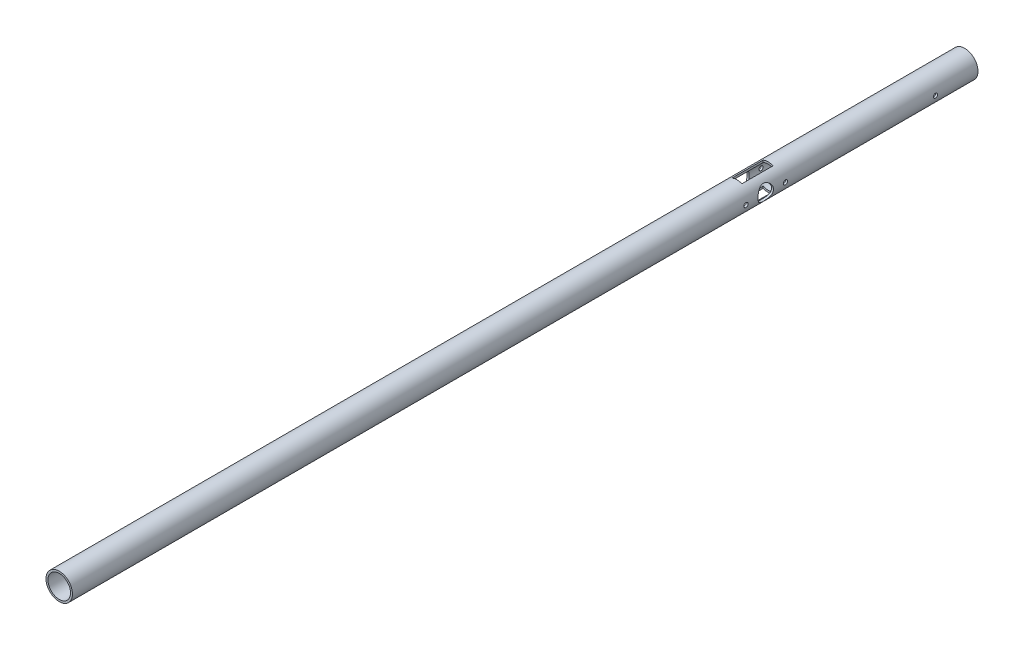
SolidWorks part; units mm, degrees
material "6061-T4 (SS)"
ref_plane "Front" through (0, 0, 0) normal (0, 0, 1) x (1, 0, 0)
ref_plane "Top" through (0, 0, 0) normal (0, 1, 0) x (1, 0, 0)
ref_plane "Right" through (0, 0, 0) normal (1, 0, 0) x (0, 0, -1)
sketch "Sketch1" plane through (0, 0, 0) normal (0, 0, 1) x (1, 0, 0)
  circle A0 centre (0, 0) radius 9.36
  circle A1 centre (0, 0) radius 7.99
extrude "Extrude1" add sketch "Sketch1" along normal blind 640
sketch "Sketch2" plane through (0, 0, 0) normal (1, 0, 0) x (0, 0, -1)
  line L0 (-30, -47.5362) -> (-30, 39.1475) construction
  line L1 (0, -9.36) -> (0, 9.36) construction
  line L2 (-150, -93.5027) -> (-150, 51.4365) construction
  line L3 (-640, 9.36) -> (-640, -9.36) construction
  circle A0 centre (-30, 0) radius 1.5
  circle A1 centre (-150, 0) radius 5.5
  circle A2 centre (-136.0625, 0) radius 1.5
  circle A3 centre (-163.9375, 0) radius 1.5
  point P10 (-163.9375, 0)
  point P11 (-136.0625, 0)
  point P16 (-640, 0)
  dimension "D2" = 150
  dimension "D3" = 13.9375
  dimension "D5" = 476.0625
  dimension "D1" = 30
  dimension "D4" = 13.9375
extrude "Extrude2" cut sketch "Sketch2" against normal through all and the other way through all
sketch "Sketch3" plane through (0, 0, 0) normal (0, 1, 0) x (1, 0, 0)
  line L0 (-54.8402, -150) -> (72.4613, -150) construction
  line L1 (7.99, 0) -> (-7.99, 0) construction
  line L2 (-44.3384, -139) -> (38.4408, -139) construction
  line L3 (-76.6388, -161) -> (67.6466, -161) construction
  line L4 (3.5, -160.8387) -> (3.5, -87.3966) construction
  line L5 (0, -179.9469) -> (0, -88.7091) construction
  line L6 (-3.5, -169.4108) -> (-3.5, -98.3485) construction
  line L8 (-3.5, -139) -> (3.5, -139)
  line L9 (-3.5, -139) -> (-3.5, -161)
  line L10 (-3.5, -161) -> (3.5, -161)
  line L11 (3.5, -139) -> (3.5, -161)
  dimension "D1" = 150
  dimension "D2" = 11
  dimension "D3" = 22
  dimension "D4" = 3.5
  dimension "D5" = 7
extrude "Extrude3" cut sketch "Sketch3" against normal blind 25 and the other way blind 25
